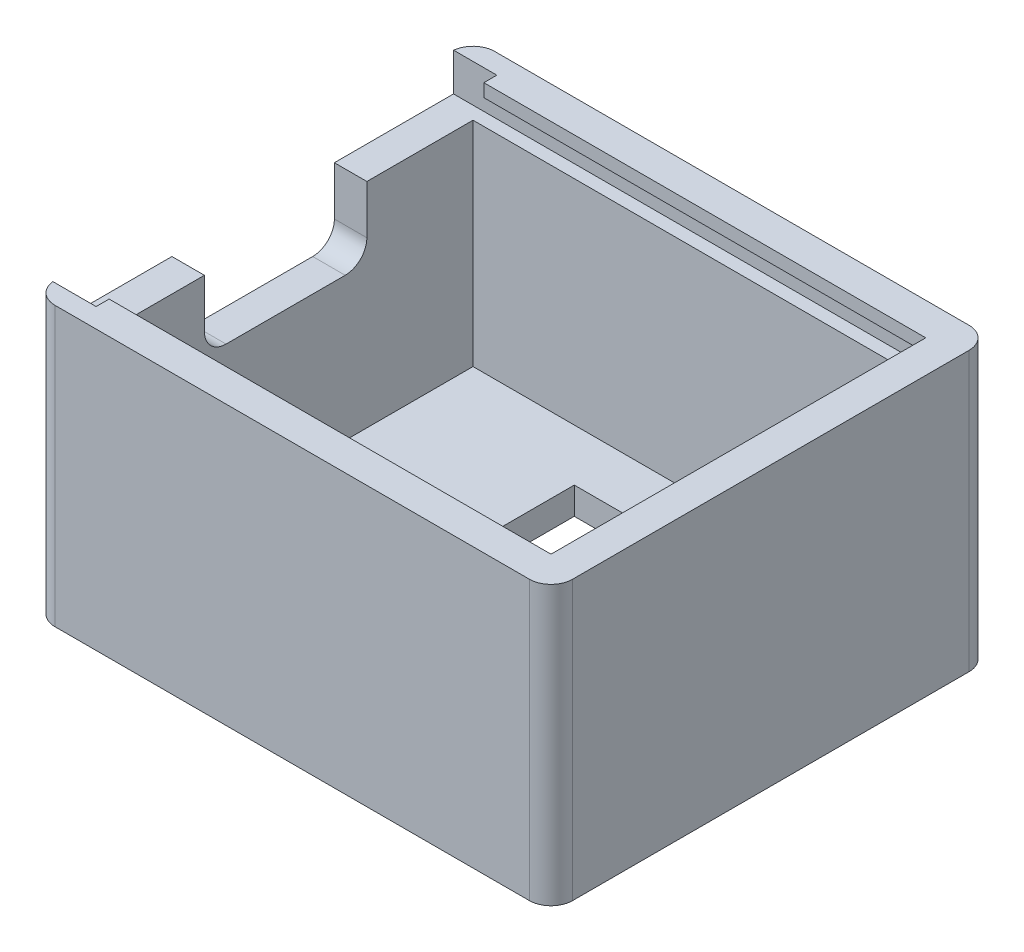
SolidWorks part; units mm, degrees
ref_plane "Front Plane" through (0, 0, 0) normal (0, 0, 1) x (1, 0, 0)
ref_plane "Top Plane" through (0, 0, 0) normal (0, 1, 0) x (1, 0, 0)
ref_plane "Right Plane" through (0, 0, 0) normal (1, 0, 0) x (0, 0, -1)
sketch "Sketch1" plane through (0, 0, 0) normal (0, 1, 0) x (1, 0, 0)
  line L1 (-23.9, 20.3) -> (23.9, 20.3)
  line L2 (-23.9, 20.3) -> (-23.9, -20.3)
  line L3 (-23.9, -20.3) -> (23.9, -20.3)
  line L4 (23.9, 20.3) -> (23.9, -20.3)
  line L5 (-23.9, 20.3) -> (23.9, -20.3) construction
  line L6 (-23.9, -20.3) -> (23.9, 20.3) construction
  point P0 (0, 0)
  dimension "D1" = 47.8
  dimension "D2" = 40.6
extrude "Boss-Extrude1" add sketch "Sketch1" along normal blind 25.7
sketch "Sketch2" plane through (0, 25.7, 0) normal (0, 1, 0) x (1, 0, 0)
  line L1 (-20.9, 17.3) -> (20.9, 17.3)
  line L2 (-20.9, 17.3) -> (-20.9, -17.3)
  line L3 (-20.9, -17.3) -> (20.9, -17.3)
  line L4 (20.9, 17.3) -> (20.9, -17.3)
  line L5 (-20.9, 17.3) -> (20.9, -17.3) construction
  line L6 (-20.9, -17.3) -> (20.9, 17.3) construction
  point P1 (0, 0)
  dimension "D1" = 41.8
  dimension "D2" = 34.6
extrude "Cut-Extrude1" cut sketch "Sketch2" against normal blind 23.2
fillet "Fillet1" radius 2 4 edges at (23.9, 12.85, -20.3) (-23.9, 12.85, -20.3) (-23.9, 12.85, 20.3) (23.9, 12.85, 20.3)
sketch "Sketch3" plane through (0, 2.5, 0) normal (0, 1, 0) x (1, 0, 0)
  line L1 (-6.75, 12.5) -> (18.25, 12.5)
  line L2 (-6.75, 12.5) -> (-6.75, -12.5)
  line L3 (-6.75, -12.5) -> (18.25, -12.5)
  line L4 (18.25, 12.5) -> (18.25, -12.5)
  line L5 (-6.75, 12.5) -> (18.25, -12.5) construction
  line L6 (-6.75, -12.5) -> (18.25, 12.5) construction
  point P0 (5.75, 0)
  dimension "D1" = 25
  dimension "D2" = 25
  dimension "D3" = 5.75
extrude "Cut-Extrude2" cut sketch "Sketch3" against normal through all
sketch "Sketch4" plane through (0, 0, 0) normal (0, 1, 0) x (1, 0, 0)
  line L0 (-23.9, 0) -> (23.9, 0) construction
  line L1 (-23.9, 18.3) -> (-23.9, -18.3) construction
  line L2 (23.9, -18.3) -> (23.9, 18.3) construction
  line L4 (-24.9, 18.5) -> (22.1, 18.5)
  line L5 (-24.9, 18.5) -> (-24.9, -18.5)
  line L6 (-24.9, -18.5) -> (22.1, -18.5)
  line L7 (22.1, 18.5) -> (22.1, -18.5)
  dimension "D1" = 37
  dimension "D2" = 22.1
  dimension "D3" = 24.9
extrude "Cut-Extrude3" cut sketch "Sketch4" along normal blind 2.3 from offset 22.2
sketch "Sketch6" plane through (-23.9, 0, 0) normal (-1, 0, 0) x (0, 0, 1)
  line L0 (-18.3, 25.7) -> (18.3, 25.7) construction
  line L1 (-18.5, 27.45) -> (18.5, 27.45)
  line L2 (-18.5, 27.45) -> (-18.5, 23.95)
  line L3 (-18.5, 23.95) -> (18.5, 23.95)
  line L4 (18.5, 27.45) -> (18.5, 23.95)
  line L5 (-18.5, 27.45) -> (18.5, 23.95) construction
  line L6 (-18.5, 23.95) -> (18.5, 27.45) construction
  point P0 (0, 25.7)
  dimension "D1" = 37
extrude "Cut-Extrude4" cut sketch "Sketch6" against normal blind 4
sketch "Sketch7" plane through (-23.9, 0, 0) normal (-1, 0, 0) x (0, 0, 1)
  line L0 (-18.3, 22.2) -> (18.3, 22.2) construction
  line L1 (-7.5, 28.7) -> (7.5, 28.7)
  line L2 (-7.5, 28.7) -> (-7.5, 15.7)
  line L3 (-7.5, 15.7) -> (7.5, 15.7)
  line L4 (7.5, 28.7) -> (7.5, 15.7)
  line L5 (-7.5, 28.7) -> (7.5, 15.7) construction
  line L6 (-7.5, 15.7) -> (7.5, 28.7) construction
  point P0 (0, 22.2)
  dimension "D1" = 15
  dimension "D2" = 13
extrude "Cut-Extrude5" cut sketch "Sketch7" against normal blind 4
fillet "Fillet2" radius 2 2 edges at (-22.4, 15.7, 7.5) (-22.4, 15.7, -7.5)
equation "\"board_w\"= 33.8"
equation "\"board_l\"= 41"
equation "\"stack_h\"= 19.5"
equation "\"module_w\"= 9.9"
equation "\"lens_d\"= 7.8"
equation "\"lens_from_end\"= 8"
equation "\"usb_w\"= 13"
equation "\"plug_h\"= 7"
equation "\"usb_from_back\"= 6"
equation "\"clear\"= 0.4"
equation "\"wall\"= 3"
equation "\"floor_t\"= 2.5"
equation "\"pocket_clear\"= 0.3"
equation "\"lens_clear\"= 0.6"
equation "\"plate_w\"= 16"
equation "\"plate_clear\"= 0.3"
equation "\"plate_t\"= 1.2"
equation "\"plate_seat\"= 0.8"
equation "\"window_d\"= 12"
equation "\"lid_t\"= 2"
equation "\"lid_gap\"= 1"
equation "\"groove_d\"= 1.2"
equation "\"groove_clear\"= 0.15"
equation "\"lip_top\"= 1.2"
equation "\"side_clear\"= 0.2"
equation "\"slide_clear\"= 0.2"
equation "\"ball_d\"= 16"
equation "\"ball_clear\"= 0.3"
equation "\"lip\"= 1.2"
equation "\"cup_floor\"= 1.2"
equation "\"cup_d\"= \"ball_d\" + \"ball_clear\" + 2 * \"finger_t\""
equation "\"slit_w\"= 1.5"
equation "\"slit_depth\"= 9"
equation "\"lug_w\"= 16"
equation "\"m3_hole\"= 3.4"
equation "\"m3_nut\"= 5.7"
equation "\"m3_nut_d\"= 2.6"
equation "\"boss_d\"= 20"
equation "\"boss_h\"= 8"
equation "\"nut_af\"= 11.4"
equation "\"nut_t\"= 5.8"
equation "\"screw_hole\"= 6.6"
equation "\"in_l\"= \"board_l\" + 2 * \"clear\""
equation "\"in_w\"= \"board_w\" + 2 * \"clear\""
equation "\"out_l\"= \"in_l\" + 2 * \"wall\""
equation "\"out_w\"= \"in_w\" + 2 * \"wall\""
equation "\"y_groove\"= \"floor_t\" - \"plate_seat\" + \"stack_h\" + \"lid_gap\""
equation "\"groove_h\"= \"lid_t\" + 2 * \"groove_clear\""
equation "\"tray_h\"= \"y_groove\" + \"groove_h\" + \"lip_top\""
equation "\"lid_w\"= \"in_w\" + 2 * \"groove_d\" - 2 * \"side_clear\""
equation "\"lid_right\"= \"in_l\" / 2 + \"groove_d\" - \"slide_clear\""
equation "\"lid_left\"= \"out_l\" / 2"
equation "\"open_d\"= \"ball_d\" - 2 * \"lip\""
equation "\"c_ball\"= sqr( ( ( \"ball_d\" + \"ball_clear\" ) / 2 ) ^ 2 - ( \"open_d\" / 2 ) ^ 2 )"
equation "\"cup_h\"= \"cup_floor\" + ( \"ball_d\" + \"ball_clear\" ) / 2 + \"c_ball\""
equation "\"lug_in\"= \"cup_d\" / 2 - 5"
equation "\"lug_out\"= \"cup_d\" / 2 + 4"
equation "\"D2@Sketch1\"=\"out_w\""
equation "\"D1@Sketch1\"=47.80mm"
equation "\"D1@Boss-Extrude1\"=\"tray_h\""
equation "\"D1@Sketch2\"=\"in_l\""
equation "\"D2@Sketch2\"=\"in_w\""
equation "\"D1@Cut-Extrude1\"=\"tray_h\"-\"floor_t\""
equation "\"D1@Sketch4\"=\"in_w\" + 2 * \"groove_d\""
equation "\"D2@Sketch4\"= \"in_l\" / 2 + \"groove_d\""
equation "\"D3@Sketch4\"=\"out_l\" / 2 + 1"
equation "\"D19@Cut-Extrude3\"=\"y_groove\""
equation "\"D1@Cut-Extrude3\"=\"groove_h\""
equation "\"D1@Sketch6\"=\"in_w\"+2 * \"groove_d\""
equation "\"D2@Sketch6\"=\"groove_h\"+ \"lip_top\""
equation "\"D1@Cut-Extrude4\"=\"wall\"+1"
equation "\"D1@Sketch7\"= \"lid_gap\" + \"groove_h\" + \"lip_top\" + \"usb_from_back\" + \"plug_h\" / 2 + 1"
equation "\"D2@Sketch7\"=\"usb_w\""
equation "\"D1@Cut-Extrude5\"=\"wall\"+1"
